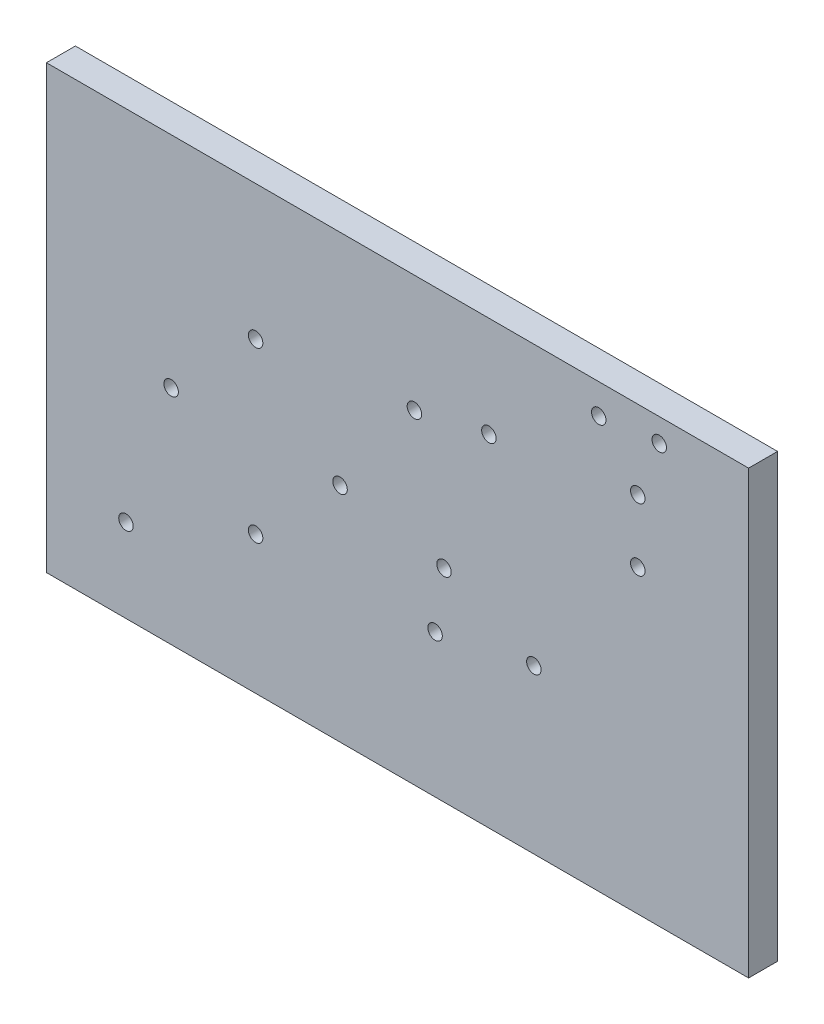
SolidWorks part; units mm, degrees
ref_plane "Front Plane" through (0, 0, 0) normal (0, 0, 1) x (1, 0, 0)
ref_plane "Top Plane" through (0, 0, 0) normal (0, 1, 0) x (1, 0, 0)
ref_plane "Right Plane" through (0, 0, 0) normal (1, 0, 0) x (0, 0, -1)
sketch "Sketch1" plane through (0, 0, 0) normal (0, 0, 1) x (1, 0, 0)
  line L0 (-152.4, 0) -> (155.575, 0) construction
  line L5 (155.575, -88.9) -> (-152.4, -88.9)
  line L7 (155.575, 104.775) -> (-152.4, 104.775)
  line L11 (-152.4, 104.775) -> (-152.4, 0)
  line L12 (-152.4, 0) -> (-152.4, -88.9)
  line L13 (155.575, 104.775) -> (155.575, 0)
  line L14 (155.575, 0) -> (155.575, -88.9)
  point P0 (0, 0)
  dimension "D1" = 307.975
  dimension "D2" = 104.775
  dimension "D3" = 88.9
extrude "Boss-Extrude1" add sketch "Sketch1" along normal blind 12.7
sketch "Sketch3" plane through (0, 0, 12.7) normal (0, 0, 1) x (1, 0, 0)
  line L0 (79.4805, 56.6481) -> (134.4715, 56.6481) construction
  line L1 (106.976, 84.1436) -> (106.976, 29.1526) construction
  line L2 (106.976, 56.6481) -> (129.2693, 72.7418) construction
  line L3 (-60.6634, 61.021) -> (-60.6634, -43.754) construction
  line L4 (-60.6634, -43.754) -> (-113.0509, 8.6335) construction
  line L5 (-113.0509, 8.6335) -> (-8.2759, 8.6335) construction
  line L6 (-8.2759, 8.6335) -> (-60.6634, -43.754) construction
  line L7 (-60.6634, 61.021) -> (-8.2759, 8.6335) construction
  line L8 (-60.6634, 61.021) -> (-113.0509, 8.6335) construction
  line L9 (-123.1002, -29.7104) -> (-113.7768, -67.425) construction
  line L10 (-129.223, -72.8028) -> (-98.3305, -62.0472) construction
  line L11 (-135.7992, -71.318) -> (-107.8952, -42.3951) construction
  line L12 (-94.0886, -56.7145) -> (-132.8992, -49.3817) construction
  line L13 (-128.1499, -34.1078) -> (-137.6485, -64.6556) construction
  line L14 (-5.9191, -41.6851) -> (81.3252, 14.7236) construction
  line L15 (7.6026, 12.3208) -> (37.703, -13.4807) construction
  line L16 (37.703, -13.4807) -> (85.0636, -21.2671) construction
  line L17 (-7.7928, 49.7758) -> (58.4342, 64.3503) construction
  line L18 (68.0072, -40.2298) -> (102.1201, -2.3043) construction
  arc A0 (99.4052, 83.0808) -> (114.5467, 30.2154) centre (106.976, 56.6481) ccw construction
  arc A1 (114.5467, 30.2154) -> (99.4052, 83.0808) centre (106.976, 56.6481) ccw construction
  circle A3 centre (106.976, 70.3959) radius 3.175
  circle A5 centre (106.976, 42.9004) radius 3.175
  arc A7 (-46.2388, -41.729) -> (-75.088, 58.996) centre (-60.6634, 8.6335) ccw construction
  arc A8 (-75.088, 58.996) -> (-46.2388, -41.729) centre (-60.6634, 8.6335) ccw construction
  circle A9 centre (-60.6634, 8.6335) radius 37.0436 construction
  circle A10 centre (-60.6634, 45.677) radius 3.175
  circle A12 centre (-23.6198, 8.6335) radius 3.175
  circle A14 centre (-60.6634, -28.4101) radius 3.175
  circle A16 centre (-97.707, 8.6335) radius 3.175
  arc A18 (-116.9053, -32.252) -> (-128.1499, -34.1078) centre (-122.062, -36.0008) ccw construction
  arc A19 (-116.9053, -32.252) -> (-97.0871, -50.5956) centre (-60.6634, 8.6335) ccw construction
  arc A20 (-98.3305, -62.0472) -> (-97.0871, -50.5956) centre (-100.4267, -56.0263) ccw construction
  circle A21 centre (-117.5189, -52.2876) radius 3.175
  arc A26 (-1.7988, 40.6172) -> (-15.1981, 57.8362) centre (-60.6634, 8.6335) ccw construction
  arc A27 (59.962, 70.9768) -> (57.8357, 57.5764) centre (106.976, 56.6481) ccw construction
  circle A29 centre (8.9855, 53.4682) radius 3.175
  circle A30 centre (41.6559, 60.6579) radius 3.175
  arc A32 (-5.1254, -28.8301) -> (4.9317, -48.6235) centre (5.4032, -35.9322) ccw construction
  arc A33 (67.7408, 27.047) -> (98.4818, 8.2387) centre (106.976, 56.6481) ccw construction
  circle A34 centre (18.0623, -26.1797) radius 3.175
  arc A36 (10.9032, 14.6132) -> (6.329, 8.5093) centre (12.7044, 8.4975) ccw construction
  circle A37 centre (21.9762, 0) radius 3.175
  circle A38 centre (61.3833, -17.3739) radius 3.175
  circle A39 centre (-86.8572, 34.8272) radius 3.175 [skipped]
  circle A40 centre (-34.4697, 34.8272) radius 3.175 [skipped]
  circle A41 centre (-34.4697, -17.5603) radius 3.175 [skipped]
  circle A42 centre (-86.8572, -17.5603) radius 3.175 [skipped]
  circle A43 centre (93.2282, 56.6481) radius 3.175 [skipped]
  circle A44 centre (120.7237, 56.6481) radius 3.175 [skipped]
  circle A45 centre (89.8428, 91.6832) radius 3.175
  circle A46 centre (116.3712, 94.4995) radius 3.175
  point P26 (106.976, 56.6481)
  point P56 (-60.6634, 8.6335)
  point P75 (-117.5189, -52.2876)
  dimension "D3" = 6.35
  dimension "D4" = 6.35
  dimension "D2" = 4
  dimension "D6" = 6.35
  dimension "D7" = 6.35
  dimension "D8" = 6.35
  dimension "D9" = 6.35
  dimension "D10" = 6.35
  dimension "D11" = 6.35
  dimension "D12" = 6.35
  dimension "D13" = 6.35
  dimension "D1" = 13.7477
  dimension "D5" = 8
extrude "Cut-Extrude1" cut sketch "Sketch3" against normal through all and the other way through all
